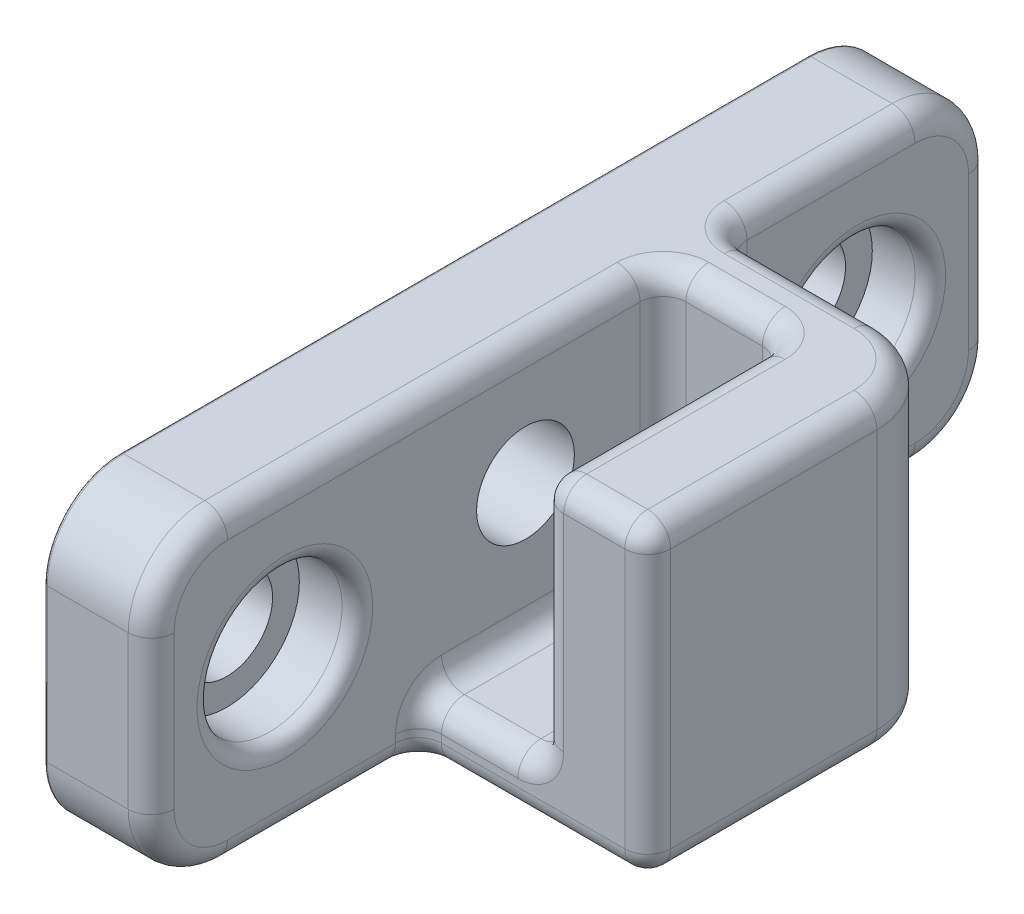
SolidWorks part; units mm, degrees
ref_plane "Front Plane" through (0, 0, 0) normal (0, 0, 1) x (1, 0, 0)
ref_plane "Top Plane" through (0, 0, 0) normal (0, 1, 0) x (1, 0, 0)
ref_plane "Right Plane" through (0, 0, 0) normal (1, 0, 0) x (0, 0, -1)
sketch "Sketch1" plane through (0, 0, 0) normal (0, 1, 0) x (1, 0, 0)
  line L1 (9, 3) -> (-11, 3) construction
  line L3 (9, -3) -> (-11, -3) construction
  line L5 (-11, 3) -> (-11, -3) construction
  line L6 (9, 3) -> (9, -3) construction
  line L16 (-11, -24.5) -> (-11, 30.5)
  line L17 (-11, 30.5) -> (-4, 30.5)
  line L18 (-4, 30.5) -> (-4, 13)
  line L19 (-4, 13) -> (11, 13)
  line L20 (11, 13) -> (11, -7)
  line L21 (11, -7) -> (4, -7)
  line L22 (4, -7) -> (4, 9)
  line L23 (4, 9) -> (-4, 9)
  line L24 (-4, 9) -> (-4, -24.5)
  line L25 (-4, -24.5) -> (-11, -24.5)
  line L26 (4, -7) -> (-4, -7)
  point P16 (0, 9)
  point P17 (9, 0)
  dimension "D1" = 6
  dimension "D2" = 7
  dimension "D3" = 17.5
  dimension "D4" = 4
  dimension "D5" = 6
  dimension "D6" = 8
  dimension "D7" = 2
  dimension "D8" = 17.5
  dimension "D9" = 4
  dimension "D10" = 5
extrude "Boss-Extrude1" add sketch "Sketch1" along normal mid plane 20 contours L25 L24 L23 L22 L21 L20 L19 L18 L17 L16 region at (-10.4076, 0, -3)
extrude "Boss-Extrude2" add sketch "Sketch1<3>" along normal blind 3.5 from surface contours L26 L22 L23 L24 region at (0, 0, -1) starting at face at (-0.8, -10, -4.2)
sketch "Sketch1<3>" plane through (0, 0, 0) normal (0, 1, 0) x (1, 0, 0) same geometry as "Sketch1"
sketch "Sketch2" plane through (-11, 0, 0) normal (-1, 0, 0) x (0, 0, 1)
  line L0 (24.5, 10) -> (-30.5, 10) construction
  line L1 (-30.5, 10) -> (-30.5, -10) construction
  line L2 (24.5, 10) -> (24.5, -10) construction
  circle A0 centre (-21.75, 0) radius 3
  circle A1 centre (0, 2) radius 3.2
  circle A2 centre (15.75, 0) radius 3
  circle A3 centre (-21.75, 0) radius 4.75
  circle A4 centre (15.75, 0) radius 4.75
  point P8 (-23.1953, -1.8204)
  point P9 (16.6264, -2.3324)
  point P13 (0, 0)
  dimension "D1" = 6.4
  dimension "D3" = 9.5
  dimension "D4" = 6
  dimension "D5" = 4
  dimension "D6" = 4
  dimension "D2" = 8
extrude "Cut-Extrude1" cut sketch "Sketch2" against normal offset from surface (20 mm away) 2 contours A1 region at (-11, 2, 0) up to face at (11, 0, -3)
extrude "Cut-Extrude2" cut sketch "Sketch2<4>" against normal up to surface (7 mm away) contours A0 | A2 region at (-11, 0, -21.75) region at (-11, 0, 15.75) up to face at (-4, 0, -21.75)
sketch "Sketch2<4>" plane through (-11, 0, 0) normal (-1, 0, 0) x (0, 0, 1) same geometry as "Sketch2"
extrude "Cut-Extrude5" cut sketch "Sketch2<6>" along normal offset from surface (3.8 mm away) 3.2 from surface contours A3 A0 | A4 A2 region at (-11, 0, -26.3656) region at (-11, 0, 11.1344) up to face at (-11, 0, -18.75) starting at face at (-4, 0, -24.75)
sketch "Sketch2<6>" plane through (-11, 0, 0) normal (-1, 0, 0) x (0, 0, 1) same geometry as "Sketch2"
sketch "Sketch4" plane through (9, 0, 0) normal (-1, 0, 0) x (0, 0, 1)
  line L0 (-1.5, 3.5) -> (-1.5, 0.5)
  line L1 (3.2, 3.5) -> (-3.2, 3.5)
  line L2 (3.2, 3.5) -> (3.2, 0.5)
  line L3 (3.2, 0.5) -> (-3.2, 0.5)
  line L4 (-3.2, 3.5) -> (-3.2, 0.5)
  line L5 (3.2, 3.5) -> (-3.2, 0.5) construction
  line L6 (3.2, 0.5) -> (-3.2, 3.5) construction
  line L7 (1.5, 3.5) -> (1.5, 0.5)
  line L8 (-1.5, 2) -> (1.5, 2) construction
  circle A0 centre (0, 2) radius 3.2 construction
  circle A1 centre (0, 2) radius 3.2
  point P13 (0, 2)
  circle M7 centre (0, 2) radius 3.2
  dimension "D1" = 1.5
extrude "Cut-Extrude9" cut sketch "Sketch4" against normal blind 0.3 contours L3 L0 L1 M7 | L7 L1 L0 L3 | L1 L7 L3 M7 region at (9, 2, 0) region at (9, 2, -2.2932) region at (9, 2, 2.2932)
extrude "Cut-Extrude10" cut sketch "Sketch4<3>" against normal blind 0.3 from surface contours L7 L1 L0 L3 region at (9, 2, 0) starting at face at (9.3, 2, 0)
sketch "Sketch4<3>" plane through (9, 0, 0) normal (-1, 0, 0) x (0, 0, 1) same geometry as "Sketch4"
fillet "Fillet1" radius 5 5 edges at (11, 0, -13) (-7.5, -10, -30.5) (-7.5, 10, -30.5) (-7.5, 10, 24.5) (-7.5, -10, 24.5)
fillet "Fillet2" radius 1.5 30 edges at (-4, 0, -30.5) (-4, -8.5355, -29.0355) (-4, 8.5355, -29.0355) (-4, -10, -19.25) (-4, 10, -19.25) (4, 10, -1) (1, -10, -13) (9.5355, -10, -11.5355) (1, 10, -13) (9.5355, 10, -11.5355) (-4, 10, 5.25) (-4, 8.5355, 23.0355) (-4, 0, 24.5) (-4, -8.5355, 23.0355) (0, 10, -9) (4, 1.75, -9) (-4, 1.75, -9) (-4, -8.25, 7) (4, 1.75, 7) (7.5, 10, 7) (11, 0, 7) (3.5, -10, 7) (0, -6.5, -9) (4, -6.5, -1) (0, -6.5, 7) (-4, -6.5, -1) (-4, 0, -13) (11, -10, -0.5) (11, 10, -0.5) (-4, -10, 13.25)
fillet "Fillet3" radius 1 2 edges at (-4, 0, 11) (-4, 0, -26.5)
fillet "Fillet4" radius 0.2 11 edges at (-11, 8.5355, -29.0355) (-11, 10, -3) (-11, 8.5355, 23.0355) (-11, 0, 24.5) (-11, -8.5355, 23.0355) (-11, -10, -3) (-11, -8.5355, -29.0355) (-11, 0, -30.5) (-11, 2, 3.2) (-11, 0, 18.75) (-11, 0, -18.75)
